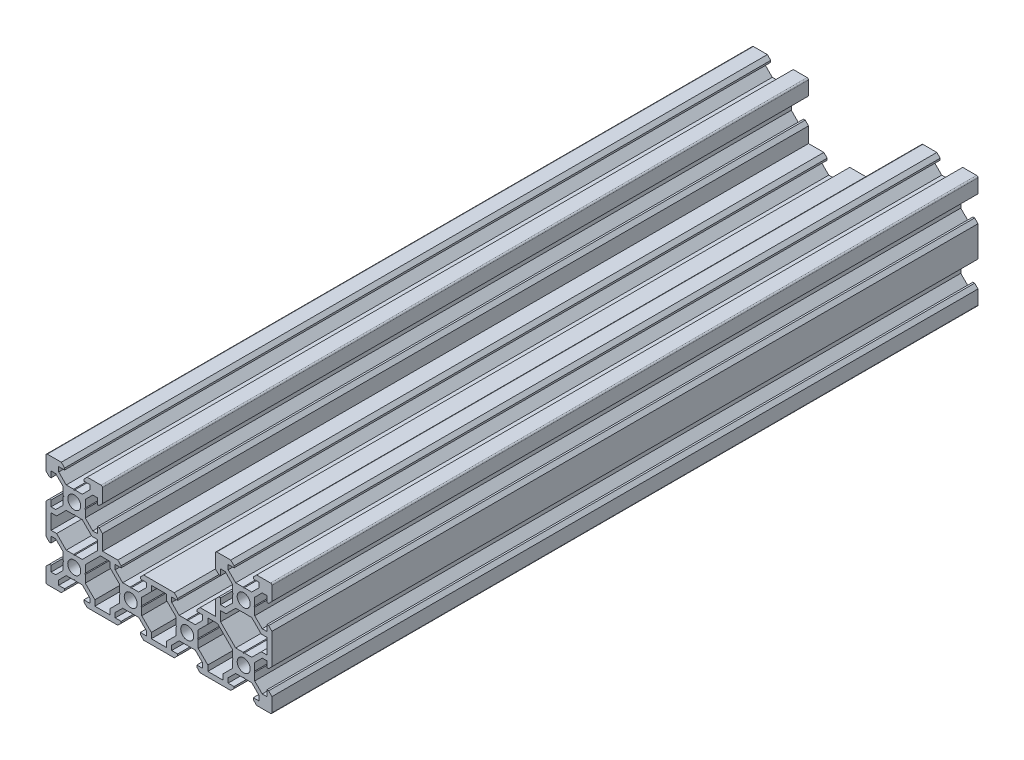
SolidWorks part; units mm, degrees
material "6063-T5"
ref_plane "Plan de face" through (0, 0, 0) normal (0, 0, 1) x (1, 0, 0)
ref_plane "Plan de dessus" through (0, 0, 0) normal (0, 1, 0) x (1, 0, 0)
ref_plane "Plan de droite" through (0, 0, 0) normal (1, 0, 0) x (0, 0, -1)
sketch "Esquisse1" plane through (0, 0, 0) normal (0, 0, 1) x (1, 0, 0)
  line L0 (-3.9, 2.8393) -> (-6.5607, 5.5)
  line L1 (-3.9, 3.9) -> (3.9, 3.9) construction
  line L2 (-3.9, 3.9) -> (-3.9, -3.9) construction
  line L3 (-3.9, -3.9) -> (3.9, -3.9) construction
  line L4 (3.9, 3.9) -> (3.9, -3.9) construction
  line L5 (-3.9, 3.9) -> (3.9, -3.9) construction
  line L6 (-3.9, -3.9) -> (3.9, 3.9) construction
  line L7 (-2.8393, 3.9) -> (-5.5, 6.5607)
  line L8 (-6.5607, 5.5) -> (-8.2, 5.5)
  line L9 (-8.2, 5.5) -> (-8.2, 3.395)
  line L10 (-8.2, 3.395) -> (-8.815, 3.395)
  line L11 (-8.815, 3.395) -> (-10, 4.58)
  line L12 (-10, 4.58) -> (-10, 9.5)
  line L13 (-4.58, 10) -> (-9.5, 10)
  line L14 (-3.395, 8.815) -> (-4.58, 10)
  line L15 (-3.395, 8.2) -> (-3.395, 8.815)
  line L16 (-5.5, 8.2) -> (-3.395, 8.2)
  line L17 (-5.5, 6.5607) -> (-5.5, 8.2)
  line L18 (0, 7.4695) -> (0, -30) construction
  line L19 (5.5, 6.5607) -> (5.5, 8.2)
  line L20 (5.5, 8.2) -> (3.395, 8.2)
  line L21 (3.395, 8.2) -> (3.395, 8.815)
  line L22 (3.395, 8.815) -> (4.58, 10)
  line L23 (4.58, 10) -> (9.5, 10)
  line L24 (10, 4.58) -> (10, 9.5)
  line L25 (8.815, 3.395) -> (10, 4.58)
  line L26 (8.2, 3.395) -> (8.815, 3.395)
  line L27 (8.2, 5.5) -> (8.2, 3.395)
  line L28 (6.5607, 5.5) -> (8.2, 5.5)
  line L29 (2.8393, 3.9) -> (5.5, 6.5607)
  line L30 (3.9, 2.8393) -> (6.5607, 5.5)
  line L31 (-2.8393, 3.9) -> (2.8393, 3.9)
  line L32 (-3.9, -2.8393) -> (-6.5607, -5.5)
  line L33 (-2.8393, -3.9) -> (-6.2393, -7.3)
  line L34 (-3.9, 2.8393) -> (-3.9, -2.8393)
  line L35 (-6.5607, -5.5) -> (-8.2, -5.5)
  line L36 (-8.2, -5.5) -> (-8.2, -3.395)
  line L37 (-8.2, -3.395) -> (-8.815, -3.395)
  line L38 (-8.815, -3.395) -> (-10, -4.58)
  line L39 (-10, -4.58) -> (-10, -15.42)
  line L40 (-6.2393, -7.3) -> (-8.2, -7.3)
  line L41 (-8.2, -7.3) -> (-8.2, -12.7)
  line L42 (30, -10) -> (-10, -10) construction
  line L43 (6.2393, -7.3) -> (8.2, -7.3)
  line L44 (8.2, -7.3) -> (8.2, -10.7393)
  line L45 (8.815, -3.395) -> (10, -4.58)
  line L46 (8.2, -3.395) -> (8.815, -3.395)
  line L47 (8.2, -5.5) -> (8.2, -3.395)
  line L48 (6.5607, -5.5) -> (8.2, -5.5)
  line L49 (2.8393, -3.9) -> (6.2393, -7.3)
  line L50 (3.9, -2.8393) -> (6.5607, -5.5)
  line L51 (30, 10) -> (-10, -30) construction
  line L52 (-2.8393, -3.9) -> (2.8393, -3.9)
  line L53 (3.9, 2.8393) -> (3.9, -2.8393)
  line L54 (-3.9, -16.1) -> (3.9, -23.9) construction
  line L55 (-3.9, -23.9) -> (3.9, -16.1) construction
  line L56 (-3.9, -23.9) -> (3.9, -23.9) construction
  line L57 (-3.9, -16.1) -> (3.9, -16.1) construction
  line L58 (-3.9, -23.9) -> (-3.9, -16.1) construction
  line L59 (3.9, -23.9) -> (3.9, -16.1) construction
  line L60 (16.1, -23.9) -> (23.9, -16.1) construction
  line L61 (-2.8393, -16.1) -> (2.8393, -16.1)
  line L62 (-6.2393, -12.7) -> (-8.2, -12.7)
  line L63 (-8.815, -16.605) -> (-10, -15.42)
  line L64 (-8.2, -16.605) -> (-8.815, -16.605)
  line L65 (-8.2, -14.5) -> (-8.2, -16.605)
  line L66 (-6.5607, -14.5) -> (-8.2, -14.5)
  line L67 (-3.9, -22.8393) -> (-3.9, -17.1607)
  line L68 (-2.8393, -16.1) -> (-6.2393, -12.7)
  line L69 (-3.9, -17.1607) -> (-6.5607, -14.5)
  line L70 (23.9, -23.9) -> (16.1, -16.1) construction
  line L71 (23.9, -16.1) -> (16.1, -16.1) construction
  line L72 (16.1, -23.9) -> (16.1, -16.1) construction
  line L73 (23.9, -23.9) -> (16.1, -23.9) construction
  line L74 (23.9, -23.9) -> (23.9, -16.1) construction
  line L75 (10, -4.58) -> (10, -10)
  line L76 (-2.8393, -23.9) -> (-5.5, -26.5607)
  line L77 (-10, -24.58) -> (-10, -29.5)
  line L78 (-8.815, -23.395) -> (-10, -24.58)
  line L79 (-8.2, -23.395) -> (-8.815, -23.395)
  line L80 (-8.2, -25.5) -> (-8.2, -23.395)
  line L81 (-6.5607, -25.5) -> (-8.2, -25.5)
  line L82 (-5.5, -26.5607) -> (-5.5, -28.2)
  line L83 (-3.9, -22.8393) -> (-6.5607, -25.5)
  line L84 (-5.5, -28.2) -> (-3.395, -28.2)
  line L85 (-3.395, -28.2) -> (-3.395, -28.815)
  line L86 (-3.395, -28.815) -> (-4.58, -30)
  line L87 (-4.58, -30) -> (-9.5, -30)
  line L88 (15.42, -10) -> (10, -10)
  line L89 (2.8393, -23.9) -> (5.5, -26.5607)
  line L90 (3.9, -22.8393) -> (7.3, -26.2393)
  line L91 (-2.8393, -23.9) -> (2.8393, -23.9)
  line L92 (30, -10) -> (30, -30) construction
  line L93 (5.5, -26.5607) -> (5.5, -28.2)
  line L94 (5.5, -28.2) -> (3.395, -28.2)
  line L95 (3.395, -28.2) -> (3.395, -28.815)
  line L96 (3.395, -28.815) -> (4.58, -30)
  line L97 (7.3, -26.2393) -> (7.3, -28.2)
  line L98 (3.9, -22.8393) -> (3.9, -17.1607)
  line L99 (22.8393, -16.1) -> (17.1607, -16.1)
  line L100 (16.1, -22.8393) -> (16.1, -17.1607)
  line L101 (17.1607, -16.1) -> (14.5, -13.4393)
  line L102 (16.1, -17.1607) -> (12.7, -13.7607)
  line L103 (14.5, -13.4393) -> (14.5, -11.8)
  line L104 (14.5, -11.8) -> (16.605, -11.8)
  line L105 (16.605, -11.8) -> (16.605, -11.185)
  line L106 (16.605, -11.185) -> (15.42, -10)
  line L107 (12.7, -11.8) -> (9.2607, -11.8)
  line L108 (12.7, -13.7607) -> (12.7, -11.8)
  line L109 (12.7, -28.2) -> (7.3, -28.2)
  line L110 (12.7, -26.2393) -> (12.7, -28.2)
  line L111 (15.42, -30) -> (4.58, -30)
  line L112 (16.605, -28.815) -> (15.42, -30)
  line L113 (16.605, -28.2) -> (16.605, -28.815)
  line L114 (14.5, -28.2) -> (16.605, -28.2)
  line L115 (14.5, -26.5607) -> (14.5, -28.2)
  line L116 (22.8393, -23.9) -> (17.1607, -23.9)
  line L117 (16.1, -22.8393) -> (12.7, -26.2393)
  line L118 (17.1607, -23.9) -> (14.5, -26.5607)
  line L119 (23.9, -22.8393) -> (23.9, -17.1607)
  line L120 (22.8393, -16.1) -> (25.5, -13.4393)
  line L121 (23.9, -17.1607) -> (27.3, -13.7607)
  line L122 (23.395, -11.8) -> (25.5, -11.8)
  line L123 (25.5, -11.8) -> (25.5, -13.4393)
  line L124 (23.395, -11.8) -> (23.395, -11.185)
  line L125 (23.395, -11.185) -> (24.58, -10)
  line L126 (24.58, -10) -> (30, -10)
  line L127 (27.3, -13.7607) -> (27.3, -11.8)
  line L128 (27.3, -11.8) -> (30, -11.8)
  line L129 (23.9, -22.8393) -> (27.3, -26.2393)
  line L130 (27.3, -26.2393) -> (27.3, -28.2)
  line L131 (27.3, -28.2) -> (30, -28.2)
  line L132 (20, -16.1) -> (20, -23.9) construction
  line L133 (10, -28.2) -> (10, -10) construction
  line L134 (30, -10) -> (30, -11.8)
  line L135 (30, -28.2) -> (30, -30)
  line L136 (2.8393, -16.1) -> (8.2, -10.7393)
  line L137 (24.58, -30) -> (30, -30)
  line L138 (23.395, -28.815) -> (24.58, -30)
  line L139 (23.395, -28.2) -> (23.395, -28.815)
  line L140 (25.5, -28.2) -> (23.395, -28.2)
  line L141 (25.5, -26.5607) -> (25.5, -28.2)
  line L142 (3.9, -17.1607) -> (9.2607, -11.8)
  line L143 (22.8393, -23.9) -> (25.5, -26.5607)
  circle A0 centre (0, 0) radius 2.3
  arc A1 (-10, 9.5) -> (-9.5, 10) centre (-9.5, 9.5) cw
  arc A2 (10, 9.5) -> (9.5, 10) centre (9.5, 9.5) ccw
  arc A3 (-10, -29.5) -> (-9.5, -30) centre (-9.5, -29.5) ccw
  circle A4 centre (0, -20) radius 2.3
  circle A7 centre (20, -20) radius 2.3
  point P62 (10, -10)
  point P78 (-8.2, -10)
  point P94 (10, -10)
  point P162 (10, -28.2)
  dimension "D1" = 4.6
  dimension "D3" = 0.5
  dimension "D2" = 1.5
  dimension "D4" = 20
  dimension "D5" = 11
  dimension "D6" = 9.16
  dimension "D7" = 6.79
  dimension "D8" = 1.8
  dimension "D9" = 4.3
  dimension "D10" = 1.5
  dimension "D11" = 6.79
  dimension "D15" = 1.8
extrude "Boss.-Extru.1" add sketch "Esquisse1" along normal blind 250
sketch "Esquisse2" plane through (0, 0, 250) normal (0, 0, 1) x (1, 0, 0)
  line L0 (0, 3.9) -> (0, -23.9) construction
  line L1 (2.8393, 3.9) -> (-2.8393, 3.9) construction
  line L2 (-2.8393, -23.9) -> (2.8393, -23.9) construction
  line L3 (-10, -10) -> (30, -10) construction
  line L4 (-10, -4.58) -> (-10, -15.42) construction
  line L5 (-0.21, 3.9) -> (0, 3.69)
  line L6 (0.21, 3.9) -> (0, 3.69)
  line L7 (-0.21, 3.9) -> (0.21, 3.9)
  line L8 (-3.9, 0) -> (3.9, 0) construction
  line L9 (-3.9, 2.8393) -> (-3.9, -2.8393) construction
  line L10 (3.9, -2.8393) -> (3.9, 2.8393) construction
  line L11 (9.8536, 9.8536) -> (-10, -10) construction
  line L12 (3.9, -0.21) -> (3.9, 0.21)
  line L13 (3.9, 0.21) -> (3.69, 0)
  line L14 (3.9, -0.21) -> (3.69, 0)
  line L15 (-9.8536, 9.8536) -> (10, -10) construction
  line L16 (0.21, -3.9) -> (0, -3.69)
  line L17 (-0.21, -3.9) -> (0, -3.69)
  line L18 (0.21, -3.9) -> (-0.21, -3.9)
  line L19 (-3.9, 0.21) -> (-3.9, -0.21)
  line L20 (-3.9, -0.21) -> (-3.69, 0)
  line L21 (-3.9, 0.21) -> (-3.69, 0)
  line L22 (-3.9, -20.21) -> (-3.69, -20)
  line L23 (-3.9, -19.79) -> (-3.69, -20)
  line L24 (-3.9, -20.21) -> (-3.9, -19.79)
  line L25 (0.21, -16.1) -> (-0.21, -16.1)
  line L26 (-0.21, -16.1) -> (0, -16.31)
  line L27 (0.21, -16.1) -> (0, -16.31)
  line L28 (3.9, -19.79) -> (3.69, -20)
  line L29 (3.9, -20.21) -> (3.69, -20)
  line L30 (3.9, -19.79) -> (3.9, -20.21)
  line L31 (-0.21, -23.9) -> (0.21, -23.9)
  line L32 (0.21, -23.9) -> (0, -23.69)
  line L33 (-0.21, -23.9) -> (0, -23.69)
  line L34 (10, -10) -> (10, -30) construction
  line L35 (4.58, -30) -> (15.42, -30) construction
  line L36 (20.21, -23.9) -> (20, -23.69)
  line L37 (19.79, -23.9) -> (20, -23.69)
  line L38 (20.21, -23.9) -> (19.79, -23.9)
  line L39 (16.1, -19.79) -> (16.1, -20.21)
  line L40 (16.1, -20.21) -> (16.31, -20)
  line L41 (16.1, -19.79) -> (16.31, -20)
  line L42 (19.79, -16.1) -> (20, -16.31)
  line L43 (20.21, -16.1) -> (20, -16.31)
  line L44 (19.79, -16.1) -> (20.21, -16.1)
  line L45 (23.9, -20.21) -> (23.9, -19.79)
  line L46 (23.9, -19.79) -> (23.69, -20)
  line L47 (23.9, -20.21) -> (23.69, -20)
  arc A0 (10, 9.5) -> (9.5, 10) centre (9.5, 9.5) ccw construction
  arc A1 (-9.5, 10) -> (-10, 9.5) centre (-9.5, 9.5) ccw construction
  dimension "D1" = 45
  dimension "D2" = 0.42
extrude "Enlèv. mat.-Extru.1" cut sketch "Esquisse2" against normal through all
mirror "Symétrie1" about plane through (30, -10, 250) normal (-1, 0, 0) of "Enlèv. mat.-Extru.1", "Boss.-Extru.1"
